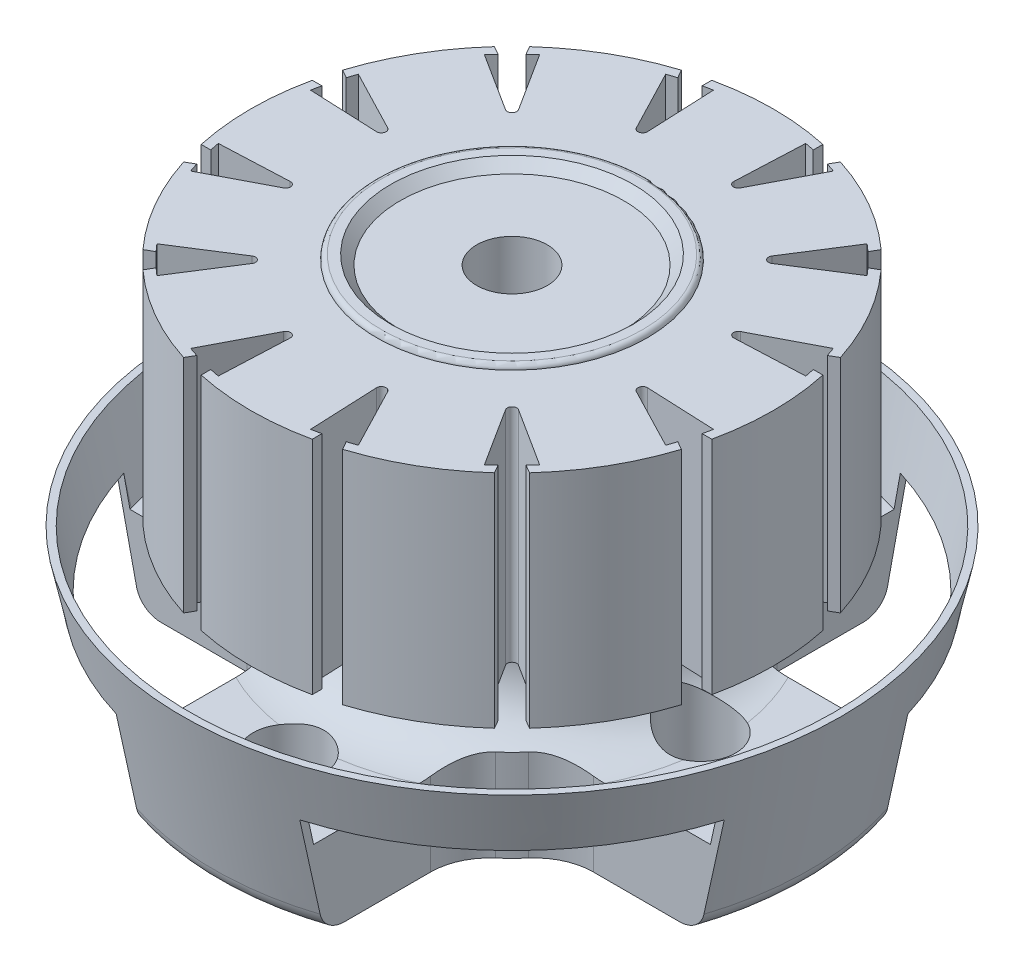
SolidWorks part; units mm, degrees
material "Cast Alloy Steel"
ref_plane "Front Plane" through (0, 0, 0) normal (0, 0, 1) x (1, 0, 0)
ref_plane "Top Plane" through (0, 0, 0) normal (0, 1, 0) x (1, 0, 0)
ref_plane "Right Plane" through (0, 0, 0) normal (1, 0, 0) x (0, 0, -1)
sketch "Sketch1" plane through (0, 0, 0) normal (0, 0, 1) x (1, 0, 0)
  line L0 (0, 0) -> (0, 17.1)
  line L1 (0, 17.1) -> (-5.75, 17.1)
  line L2 (-5.2, 0) -> (-12.5, 0)
  line L3 (-12.9328, 3.5) -> (-13.6934, 7.1)
  line L4 (-12.5, 0) -> (-12.5, 7.1) construction
  line L5 (-13.6934, 7.1) -> (-14, 7.1)
  line L6 (-12.5, 0) -> (-14, 7.1)
  line L7 (-5.75, 6.5) -> (-5.75, 17.1)
  line L8 (-8.75, 3.5) -> (-12.9328, 3.5)
  line L9 (-5.2, 3.5) -> (-12.5, 3.5) construction
  line L10 (-8.75, 3.5) -> (-5.75, 6)
  line L11 (0, 0) -> (-14, 0) construction
  line L12 (-12.2065, 0.062) -> (-13.7065, 7.162) construction
  line L14 (-12.5, 0) -> (-12.5, 28.8581) construction
  line L15 (-5.75, 0) -> (-5.75, 28.8581) construction
  line L16 (0, 7.1) -> (-14, 7.1) construction
  line L25 (0, 0) -> (0, 28.8581) construction
  line L30 (0, 0) -> (0, 43.4) construction
  line L31 (-5.2, 0) -> (-5.2, 2) construction
  line L32 (-5.2, 0) -> (-3.2, 2)
  line L33 (0, 2) -> (-3.2, 2)
  line L35 (-5.2, 0) -> (-5.2, 43.4) construction
  line L36 (0, 2) -> (-12.5, 2) construction
  line L37 (0, 0) -> (-12.5, 0) construction
  arc A0 (-5.75, 6.5) -> (-8.75, 3.5) centre (-8.75, 6.5) cw
  spline S0 degree 1 poles (-8.75, 3.5) (-5.75, 6) knots 0 0 1 1
  point P4 (-14, 28.8581)
  point P5 (0, 23.4)
  point P6 (-14, 23.4)
  point P13 (0, 20.5)
  point P14 (-14, 20.5)
  point P16 (-5.75, 23.4)
  point P18 (-5.55, 0)
  point P19 (-5.55, 28.8581)
  point P20 (0, 28.4)
  point P21 (-8.25, 28.4)
  point P22 (-5.55, 28.4)
  point P25 (-5.55, 43.4)
  point P43 (-5.75, 3.5)
  dimension "D12" = 5.2
  dimension "D11" = 3
  dimension "D14" = 45
  dimension "D2" = 14
  dimension "D5" = 5.75
  dimension "D6" = 17.1
  dimension "D9" = 3
  dimension "D10" = 2.5
  dimension "D3" = 12.5
  dimension "D4" = 7.1
  dimension "D7" = 0.3
  dimension "D8" = 3.5
  dimension "D13" = 2
revolve "Revolve1" add sketch "Sketch1" angle 360 about L30 region at (-4.4456, 7.5604, 0)
fillet "Fillet1" radius 1 1 edges at (12.5, 0, 0)
sketch "Sketch5" plane through (0, 17.1, 0) normal (0, 1, 0) x (1, 0, 0)
  circle A0 centre (0, 0) radius 4.75
  circle A1 centre (0, 0) radius 5.75 construction
  circle A2 centre (0, 0) radius 5.75
  dimension "D1" = 1
extrude "Cut-Extrude3" cut sketch "Sketch5" against normal blind 0.4 contours A0 region at (0, 17.1, 0)
fillet "Fillet5" radius 0.2 1 edges at (5.75, 17.1, 0)
chamfer "Chamfer2" distance 0.4 angle 45 1 edges at (0, 17.1, 4.75)
sketch "Sketch6" plane through (0, 16.7, 0) normal (0, 1, 0) x (1, 0, 0)
  circle A0 centre (0, 0) radius 1.5
extrude "Cut-Extrude4" cut sketch "Sketch6" against normal up to surface (14.7 mm away) up to face at (3.2, 2, 0)
sketch "Sketch2" plane through (0, 0, 0) normal (0, -1, 0) x (1, 0, 0)
  line L0 (0, 0) -> (0, 14) construction
  line L1 (0, 0) -> (-14, 0) construction
  line L2 (0, 0) -> (0, -14) construction
  line L3 (0, 0) -> (14, 0) construction
  line L4 (3.9, 3.9) -> (3.9, 6.1117)
  line L5 (-3.9, 3.9) -> (-3.9, 6.1117)
  line L6 (-3.9, 3.9) -> (-6.1117, 3.9)
  line L7 (3.9, -3.9) -> (6.1117, -3.9)
  line L8 (-3.9, -3.9) -> (-3.9, -6.1117)
  line L9 (-3.9, -3.9) -> (-6.1117, -3.9)
  line L10 (3.9, 3.9) -> (6.1117, 3.9)
  line L11 (3.9, -3.9) -> (3.9, -6.1117)
  line L12 (-3.9, 7.3554) -> (-3.9, 14)
  line L13 (-3.9, 0) -> (-3.9, 14) construction
  line L14 (0, 3.9) -> (-14, 3.9) construction
  line L15 (0, 3.9) -> (14, 3.9) construction
  line L16 (3.9, 0) -> (3.9, 14) construction
  line L17 (3.9, 0) -> (3.9, -14) construction
  line L18 (-3.9, 0) -> (-3.9, -14) construction
  line L19 (0, -3.9) -> (-14, -3.9) construction
  line L20 (0, -3.9) -> (14, -3.9) construction
  line L21 (-7.3554, 3.9) -> (-14, 3.9)
  line L22 (3.9, 7.3554) -> (3.9, 14)
  line L23 (7.3554, 3.9) -> (14, 3.9)
  line L24 (7.3554, -3.9) -> (14, -3.9)
  line L25 (3.9, -7.3554) -> (3.9, -14)
  line L26 (-3.9, -7.3554) -> (-3.9, -14)
  line L27 (-7.3554, -3.9) -> (-14, -3.9)
  arc A0 (-4.759, 5.4694) -> (-5.4694, 4.759) centre (0, 0) ccw
  circle A1 centre (0, 0) radius 14 construction
  arc A2 (-4.759, 5.4694) -> (-3.9, 7.3554) centre (-6.4, 7.3554) ccw
  arc A3 (-7.3554, 3.9) -> (-5.4694, 4.759) centre (-7.3554, 6.4) ccw
  arc A4 (-6.1117, 3.9) -> (-6.1117, -3.9) centre (0, 0) ccw
  arc A5 (3.9, 7.3554) -> (4.759, 5.4694) centre (6.4, 7.3554) ccw
  arc A6 (3.9, 6.1117) -> (-3.9, 6.1117) centre (0, 0) ccw
  arc A7 (5.4694, 4.759) -> (7.3554, 3.9) centre (7.3554, 6.4) ccw
  arc A8 (5.4694, 4.759) -> (4.759, 5.4694) centre (0, 0) ccw
  circle A9 centre (0, 0) radius 14.5331
  arc A10 (7.3554, -3.9) -> (5.4694, -4.759) centre (7.3554, -6.4) ccw
  arc A11 (6.1117, -3.9) -> (6.1117, 3.9) centre (0, 0) ccw
  arc A12 (4.759, -5.4694) -> (3.9, -7.3554) centre (6.4, -7.3554) ccw
  arc A13 (4.759, -5.4694) -> (5.4694, -4.759) centre (0, 0) ccw
  arc A14 (-3.9, -7.3554) -> (-4.759, -5.4694) centre (-6.4, -7.3554) ccw
  arc A15 (-3.9, -6.1117) -> (3.9, -6.1117) centre (0, 0) ccw
  arc A16 (-5.4694, -4.759) -> (-7.3554, -3.9) centre (-7.3554, -6.4) ccw
  arc A17 (-5.4694, -4.759) -> (-4.759, -5.4694) centre (0, 0) ccw
  circle M13 centre (0, 0) radius 11.6892
  dimension "D1" = 3.9
  dimension "D5" = 14.5
  dimension "D2" = 3.9
  dimension "D3" = 3.9
  dimension "D4" = 3.9
extrude "Cut-Extrude1" cut sketch "Sketch2" against normal blind 4.7 contours L12 A9 L21 M13 | L21 A3 A0 A2 L12 M13 | L23 A9 L22 M13 | L25 A9 L24 M13 | A13 A12 L25 L24 A10 M13 | A17 A16 L27 L26 A14 M13 | L27 A9 L26 M13 | A8 A7 L23 L22 A5 M13 region at (-6.8279, 0, 6.8279) region at (-8.9682, 0, 8.9682) region at (6.8279, 0, 6.8279) region at (8.9682, 0, 8.9682) region at (-8.9682, 0, -8.9682) region at (-6.8279, 0, -6.8279) region at (6.8279, 0, -6.8279) region at (8.9682, 0, -8.9682)
sketch "Sketch3" plane through (0, 0, 0) normal (0, -1, 0) x (1, 0, 0)
  circle A0 centre (0, 0) radius 8 construction
  circle A1 centre (0, 0) radius 9.5 construction
  circle A2 centre (0, 9.5) radius 1.5
  circle A3 centre (0, -9.5) radius 1.5
  circle A4 centre (-8, 0) radius 1.5
  circle A5 centre (8, 0) radius 1.5
  dimension "D1" = 16
  dimension "D2" = 19
  dimension "D3" = 3
  dimension "D4" = 3
  dimension "D5" = 3
  dimension "D6" = 3
extrude "Cut-Extrude2" cut sketch "Sketch3" against normal blind 6
ref_plane "Plane1" through (0, 16.9, 0) normal (0, -1, 0) x (-1, 0, 0)
sketch "Sketch7" plane through (0, 16.9, 0) normal (0, -1, 0) x (-1, 0, 0)
  line L0 (0, 0) -> (0, 11.1)
  line L1 (2.36, 0) -> (2.36, 5.2434) construction
  line L2 (-2.36, 0) -> (-2.36, 5.2434) construction
  line L3 (1.96, 0) -> (1.96, 10.519) construction
  line L4 (2.36, 0) -> (2.36, 11.1) construction
  line L5 (-2.36, 0) -> (-2.36, 11.1) construction
  line L6 (-1.96, 0) -> (-1.96, 10.519) construction
  line L7 (-2.36, 10.4365) -> (-2.36, 10.8462)
  line L8 (2.36, 10.4365) -> (2.36, 10.8462)
  line L9 (-2.36, 0) -> (-2.36, 10.8462) construction
  line L10 (1.96, 10.519) -> (1.832, 7.5915)
  line L11 (2.36, 0) -> (2.36, 10.8462) construction
  line L12 (1.96, 0) -> (1.96, 10.8462) construction
  line L13 (-1.96, 0) -> (-1.96, 10.8462) construction
  line L14 (-1.96, 10.519) -> (-1.832, 7.5915)
  line L15 (3.1744, 10.2183) -> (3.3793, 10.5731)
  line L16 (7.2621, 7.8583) -> (7.4669, 8.2131)
  line L17 (3.5621, 10.0897) -> (2.2092, 7.4904)
  line L18 (6.9569, 8.1297) -> (5.3823, 5.6584)
  line L19 (7.8583, 7.2621) -> (8.2131, 7.4669)
  line L20 (10.2183, 3.1744) -> (10.5731, 3.3793)
  line L21 (8.1297, 6.9569) -> (5.6584, 5.3823)
  line L22 (10.0897, 3.5621) -> (7.4904, 2.2092)
  line L23 (10.4365, 2.36) -> (10.8462, 2.36)
  line L24 (10.4365, -2.36) -> (10.8462, -2.36)
  line L25 (10.519, 1.96) -> (7.5915, 1.832)
  line L26 (10.519, -1.96) -> (7.5915, -1.832)
  line L27 (10.2183, -3.1744) -> (10.5731, -3.3793)
  line L28 (7.8583, -7.2621) -> (8.2131, -7.4669)
  line L29 (10.0897, -3.5621) -> (7.4904, -2.2092)
  line L30 (8.1297, -6.9569) -> (5.6584, -5.3823)
  line L31 (7.2621, -7.8583) -> (7.4669, -8.2131)
  line L32 (3.1744, -10.2183) -> (3.3793, -10.5731)
  line L33 (6.9569, -8.1297) -> (5.3823, -5.6584)
  line L34 (3.5621, -10.0897) -> (2.2092, -7.4904)
  line L35 (2.36, -10.4365) -> (2.36, -10.8462)
  line L36 (-2.36, -10.4365) -> (-2.36, -10.8462)
  line L37 (1.96, -10.519) -> (1.832, -7.5915)
  line L38 (-1.96, -10.519) -> (-1.832, -7.5915)
  line L39 (-3.1744, -10.2183) -> (-3.3793, -10.5731)
  line L40 (-7.2621, -7.8583) -> (-7.4669, -8.2131)
  line L41 (-3.5621, -10.0897) -> (-2.2092, -7.4904)
  line L42 (-6.9569, -8.1297) -> (-5.3823, -5.6584)
  line L43 (-7.8583, -7.2621) -> (-8.2131, -7.4669)
  line L44 (-10.2183, -3.1744) -> (-10.5731, -3.3793)
  line L45 (-8.1297, -6.9569) -> (-5.6584, -5.3823)
  line L46 (-10.0897, -3.5621) -> (-7.4904, -2.2092)
  line L47 (-10.4365, -2.36) -> (-10.8462, -2.36)
  line L48 (-10.4365, 2.36) -> (-10.8462, 2.36)
  line L49 (-10.519, -1.96) -> (-7.5915, -1.832)
  line L50 (-10.519, 1.96) -> (-7.5915, 1.832)
  line L51 (-10.2183, 3.1744) -> (-10.5731, 3.3793)
  line L52 (-7.8583, 7.2621) -> (-8.2131, 7.4669)
  line L53 (-10.0897, 3.5621) -> (-7.4904, 2.2092)
  line L54 (-8.1297, 6.9569) -> (-5.6584, 5.3823)
  line L55 (-7.2621, 7.8583) -> (-7.4669, 8.2131)
  line L56 (-3.1744, 10.2183) -> (-3.3793, 10.5731)
  line L57 (-6.9569, 8.1297) -> (-5.3823, 5.6584)
  line L58 (-3.5621, 10.0897) -> (-2.2092, 7.4904)
  circle A0 centre (0, 0) radius 5.75 construction
  circle A1 centre (0, 0) radius 5.75
  arc A2 (-3.3793, 10.5731) -> (-7.4669, 8.2131) centre (0, 0) ccw
  arc A3 (2.36, 10.4365) -> (1.96, 10.519) centre (0, 0) ccw
  arc A4 (-1.96, 10.519) -> (-2.36, 10.4365) centre (0, 0) ccw
  circle A5 centre (0, 0) radius 10.7 construction
  arc A7 (7.2621, 7.8583) -> (6.9569, 8.1297) centre (0, 0) ccw
  arc A8 (3.5621, 10.0897) -> (3.1744, 10.2183) centre (0, 0) ccw
  arc A9 (10.2183, 3.1744) -> (10.0897, 3.5621) centre (0, 0) ccw
  arc A10 (8.1297, 6.9569) -> (7.8583, 7.2621) centre (0, 0) ccw
  arc A11 (10.4365, -2.36) -> (10.519, -1.96) centre (0, 0) ccw
  arc A12 (10.519, 1.96) -> (10.4365, 2.36) centre (0, 0) ccw
  arc A13 (7.8583, -7.2621) -> (8.1297, -6.9569) centre (0, 0) ccw
  arc A14 (10.0897, -3.5621) -> (10.2183, -3.1744) centre (0, 0) ccw
  arc A15 (3.1744, -10.2183) -> (3.5621, -10.0897) centre (0, 0) ccw
  arc A16 (6.9569, -8.1297) -> (7.2621, -7.8583) centre (0, 0) ccw
  arc A17 (-2.36, -10.4365) -> (-1.96, -10.519) centre (0, 0) ccw
  arc A18 (1.96, -10.519) -> (2.36, -10.4365) centre (0, 0) ccw
  arc A19 (-7.2621, -7.8583) -> (-6.9569, -8.1297) centre (0, 0) ccw
  arc A20 (-3.5621, -10.0897) -> (-3.1744, -10.2183) centre (0, 0) ccw
  arc A21 (-10.2183, -3.1744) -> (-10.0897, -3.5621) centre (0, 0) ccw
  arc A22 (-8.1297, -6.9569) -> (-7.8583, -7.2621) centre (0, 0) ccw
  arc A23 (-10.4365, 2.36) -> (-10.519, 1.96) centre (0, 0) ccw
  arc A24 (-10.519, -1.96) -> (-10.4365, -2.36) centre (0, 0) ccw
  arc A25 (-7.8583, 7.2621) -> (-8.1297, 6.9569) centre (0, 0) ccw
  arc A26 (-10.0897, 3.5621) -> (-10.2183, 3.1744) centre (0, 0) ccw
  arc A27 (-3.1744, 10.2183) -> (-3.5621, 10.0897) centre (0, 0) ccw
  arc A28 (-6.9569, 8.1297) -> (-7.2621, 7.8583) centre (0, 0) ccw
  arc A29 (-1.832, 7.5915) -> (-2.2092, 7.4904) centre (-2.0318, 7.5827) cw
  circle A30 centre (0, 0) radius 11.1 construction
  arc A31 (-5.3823, 5.6584) -> (-5.6584, 5.3823) centre (-5.551, 5.551) cw
  arc A32 (-7.5915, 1.832) -> (-7.4904, 2.2092) centre (-7.5827, 2.0318) ccw
  arc A33 (-7.4904, -2.2092) -> (-7.5915, -1.832) centre (-7.5827, -2.0318) ccw
  arc A34 (-5.3823, -5.6584) -> (-5.6584, -5.3823) centre (-5.551, -5.551) ccw
  arc A35 (-1.832, -7.5915) -> (-2.2092, -7.4904) centre (-2.0318, -7.5827) ccw
  arc A36 (2.2092, -7.4904) -> (1.832, -7.5915) centre (2.0318, -7.5827) ccw
  arc A37 (5.6584, -5.3823) -> (5.3823, -5.6584) centre (5.551, -5.551) ccw
  arc A38 (7.5915, -1.832) -> (7.4904, -2.2092) centre (7.5827, -2.0318) ccw
  arc A39 (7.4904, 2.2092) -> (7.5915, 1.832) centre (7.5827, 2.0318) ccw
  arc A40 (5.3823, 5.6584) -> (5.6584, 5.3823) centre (5.551, 5.551) ccw
  arc A41 (1.832, 7.5915) -> (2.2092, 7.4904) centre (2.0318, 7.5827) ccw
  arc A42 (-8.2131, 7.4669) -> (-10.5731, 3.3793) centre (0, 0) ccw
  arc A43 (-10.8462, 2.36) -> (-10.8462, -2.36) centre (0, 0) ccw
  arc A44 (-10.5731, -3.3793) -> (-8.2131, -7.4669) centre (0, 0) ccw
  arc A45 (-7.4669, -8.2131) -> (-3.3793, -10.5731) centre (0, 0) ccw
  arc A46 (-2.36, -10.8462) -> (2.36, -10.8462) centre (0, 0) ccw
  arc A47 (3.3793, -10.5731) -> (7.4669, -8.2131) centre (0, 0) ccw
  arc A48 (8.2131, -7.4669) -> (10.5731, -3.3793) centre (0, 0) ccw
  arc A49 (10.8462, -2.36) -> (10.8462, 2.36) centre (0, 0) ccw
  arc A50 (10.5731, 3.3793) -> (8.2131, 7.4669) centre (0, 0) ccw
  arc A51 (7.4669, 8.2131) -> (3.3793, 10.5731) centre (0, 0) ccw
  arc A52 (2.36, 10.8462) -> (-2.36, 10.8462) centre (0, 0) ccw
  point P17 (10.7, 0)
  point P28 (10.615, 3.2453)
  point P119 (0, 0)
  dimension "D1" = 22.2
  dimension "D8" = 0.2
  dimension "D9" = 0.2
  dimension "D10" = 0.2
  dimension "D11" = 0.2
  dimension "D12" = 0.2
  dimension "D13" = 0.2
  dimension "D14" = 0.2
  dimension "D15" = 0.2
  dimension "D16" = 0.2
  dimension "D17" = 0.2
  dimension "D18" = 0.2
  dimension "D19" = 0.2
  dimension "D2" = 2.36
  dimension "D3" = 2.36
  dimension "D4" = 0.4
  dimension "D5" = 0.4
  dimension "D6" = 0.4
  dimension "D7" = 12
extrude "Boss-Extrude1" add sketch "Sketch7" along normal offset from surface (9.4 mm away) 4 contours A52 L7 A4 L14 A29 L58 A27 L56 A2 L55 A28 L57 A31 L54 A25 L52 A42 L51 A26 L53 A32 L50 A23 L48 A43 L47 A24 L49 A33 L46 A21 L44 A44 L43 A22 L45 A34 L42 A19 L40 A45 L39 A20 L41 A35 L38 A17 L36 A46 L35 region at (-1.1532, 16.9, -10.7242) up to face at (0, 3.5, -10.1338)
